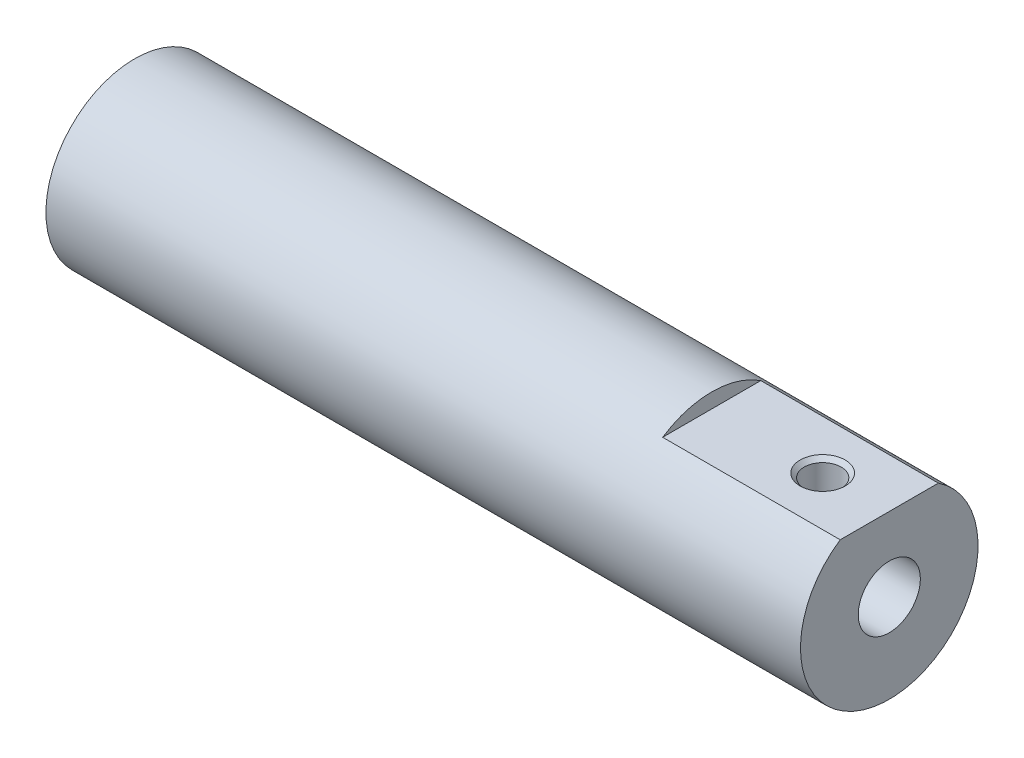
SolidWorks part; units mm, degrees
ref_plane "Front Plane" through (0, 0, 0) normal (0, 0, 1) x (1, 0, 0)
ref_plane "Top Plane" through (0, 0, 0) normal (0, 1, 0) x (1, 0, 0)
ref_plane "Right Plane" through (0, 0, 0) normal (1, 0, 0) x (0, 0, -1)
sketch "Sketch1" plane through (0, 0, 0) normal (1, 0, 0) x (0, 0, -1)
  circle A0 centre (0, 0) radius 6
  dimension "D1" = 12
extrude "Boss-Extrude1" add sketch "Sketch1" along normal blind 51
sketch "Sketch2" plane through (51, 0, 0) normal (1, 0, 0) x (0, 0, -1)
  line L0 (-3.3166, 5) -> (3.3166, 5)
  circle A0 centre (0, 0) radius 2.1
  circle A1 centre (0, 0) radius 6 construction
  arc A2 (-3.3166, 5) -> (3.3166, 5) centre (0, 0) cw
  dimension "D1" = 4.2
  dimension "D2" = 5
extrude "Cut-Extrude1" cut sketch "Sketch2" against normal blind 12
sketch "Sketch5" plane through (0, 5, 0) normal (0, 1, 0) x (1, 0, 0)
  line L0 (51, 0) -> (39, 0) construction
  line L1 (51, -3.3166) -> (51, 3.3166) construction
  line L2 (39, -3.3166) -> (39, 3.3166) construction
  point P6 (46.5, 0)
  dimension "D1" = 4.5
hole_wizard "M3 Tapped Hole1" positions "3DSketch2" profile "Sketch6" tap size "M3" standard "ISO"
sketch3d "3DSketch2"
  point P0 (46.5, 5, 0)
cosmetic thread "Hole Thread1" parameters "D1"=3.3125, "D2"=3
sketch "Sketch6" plane through (46.5, 5, 0) normal (1, 0, 0) x (0, 0, 1)
  line L0 (0, 0) -> (0, 6.7511)
  line L1 (0, 6.7511) -> (1.25, 6)
  line L2 (1.25, 6) -> (1.25, 0.275)
  line L3 (1.25, 0.275) -> (1.525, 0)
  line L5 (1.525, 0) -> (0, 0)
  line L6 (-1.25, 0.275) -> (-1.525, 0) construction
  line L10 (0, 6.7511) -> (-1.25, 6) construction
  line L11 (0, -6.35) -> (0, 107.95) construction
  dimension "Tap Drill Dia." = 2.5
  dimension "Tap Drill Depth" = 6
  dimension "Near C'Sink Dia." = 3.05
  dimension "Near C'Sink Angle" = 90
  dimension "Drill Angle" = 118
